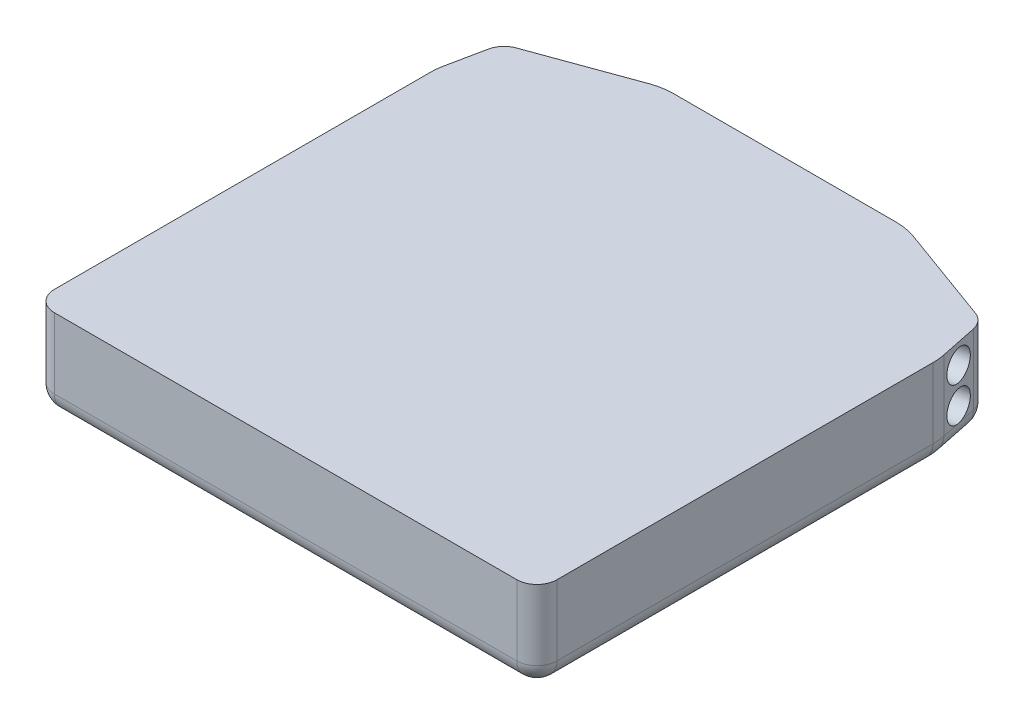
SolidWorks part; units mm, degrees
material "ABS"
ref_plane "Front Plane" through (0, 0, 0) normal (0, 0, 1) x (1, 0, 0)
ref_plane "Top Plane" through (0, 0, 0) normal (0, 1, 0) x (1, 0, 0)
ref_plane "Right Plane" through (0, 0, 0) normal (1, 0, 0) x (0, 0, -1)
sketch "Sketch1" plane through (0, 0, 0) normal (0, 1, 0) x (1, 0, 0)
  line L0 (-100, 0) -> (0, 0) construction
  line L1 (0, 118.6458) -> (-48.563, 118.6458)
  line L2 (-100, 80) -> (-100, -80)
  line L3 (-100, -80) -> (0, -80)
  line L4 (-48.563, 118.6458) -> (-95.5476, 101.5447)
  line L5 (0, 118.6458) -> (0, -80)
  line L7 (-100, 80) -> (-95.5476, 101.5447)
  line L8 (0, -80) -> (0, 118.6458) construction
  point P0 (0, 0)
  dimension "D3" = 191.676
  dimension "D6" = 50
  dimension "D1" = 22
  dimension "D2" = 160
  dimension "D4" = 200
  dimension "D5" = 100
extrude "Boss-Extrude1" add sketch "Sketch1" along normal blind 36
fillet "Fillet4" radius 8 1 edges at (-100, 18, 80)
fillet "Fillet5" radius 24 1 edges at (-100, 18, -80)
fillet "Fillet6" radius 8 1 edges at (-95.5476, 18, -101.5447)
fillet "Fillet7" radius 24 1 edges at (-48.563, 18, -118.6458)
sketch "Sketch2" plane through (0, 0, -118.6458) normal (0, 0, -1) x (-1, 0, 0)
  line L0 (44.3311, 0) -> (44.3311, 36) construction
  line L1 (0, 36) -> (44.3311, 36) construction
  line L2 (9.3311, 14) -> (9.3311, 28) construction
  line L3 (29.3311, 28) -> (31.3311, 28) construction
  line L4 (9.3311, 21) -> (0, 21) construction
  line L5 (0, 36) -> (0, 0) construction
  line L6 (0, 0) -> (44.3311, 0) construction
  circle A0 centre (37.3311, 28) radius 6
  circle A1 centre (23.3311, 28) radius 6
  circle A2 centre (9.3311, 28) radius 6
  circle A3 centre (23.3311, 14) radius 6
  circle A4 centre (9.3311, 14) radius 6
  circle A5 centre (37.3311, 14) radius 6
  circle A6 centre (0, 21) radius 2.5
  dimension "D1" = 12
  dimension "D6" = 5
  dimension "D2" = 7
  dimension "D3" = 8
  dimension "D7" = 21
  dimension "D8" = 14
  dimension "D4" = 3
  dimension "D5" = 2
extrude "Cut-Extrude1" cut sketch "Sketch2" against normal blind 10
sketch "Sketch3" plane through (-43.8128, 0, -120.3747) normal (-0.342, 0, -0.9397) x (-0.9397, 0, 0.342)
  line L0 (9.2869, 36) -> (50.591, 36) construction
  line L1 (9.2869, 36) -> (9.2869, 0) construction
  circle A0 centre (16.2869, 28) radius 6
  circle A1 centre (30.2869, 28) radius 6
  circle A2 centre (44.2869, 28) radius 6
  circle A3 centre (30.2869, 14) radius 6
  circle A4 centre (44.2869, 14) radius 6
  circle A5 centre (16.2869, 14) radius 6
  dimension "D1" = 12
  dimension "D2" = 8
  dimension "D3" = 7
  dimension "D6" = 21
  dimension "D7" = 22
  dimension "D4" = 3
  dimension "D5" = 2
extrude "Cut-Extrude2" cut sketch "Sketch3" against normal blind 10
sketch "Sketch4" plane through (-111.7597, 0, -23.096) normal (-0.9793, 0, -0.2024) x (-0.2024, 0, 0.9793)
  line L0 (-68.1013, 36) -> (-68.1013, 0) construction
  line L1 (-75.6423, 36) -> (-60.5604, 36) construction
  line L2 (-75.6423, 0) -> (-60.5604, 0) construction
  circle A0 centre (-68.1013, 28) radius 6
  circle A1 centre (-68.1013, 14) radius 6
  dimension "D1" = 12
  dimension "D3" = 2
  dimension "D2" = 8
  dimension "D4" = 22
extrude "Cut-Extrude3" cut sketch "Sketch4" against normal blind 10
mirror "Mirror2" of "Cut-Extrude3", "Cut-Extrude2", "Cut-Extrude1", "Fillet7", "Fillet6", "Fillet5", "Fillet4", "Boss-Extrude1"
fillet "Fillet3" radius 8 16 edges at (-100, 0, -2.773) (0, 0, 80) (0, 0, -118.6458) (-71.9462, 0, -110.135) (-97.9772, 0, -89.7881) (-48.4987, 0, -118.2811) (-94.6691, 0, -100.7854) (-99.8755, 0, -79.9873) (-97.6569, 0, 77.6569) (97.6569, 0, 77.6569) (100, 0, -2.773) (99.8755, 0, -79.9873) (97.9772, 0, -89.7881) (94.6691, 0, -100.7854) (71.9462, 0, -110.135) (48.4987, 0, -118.2811)
